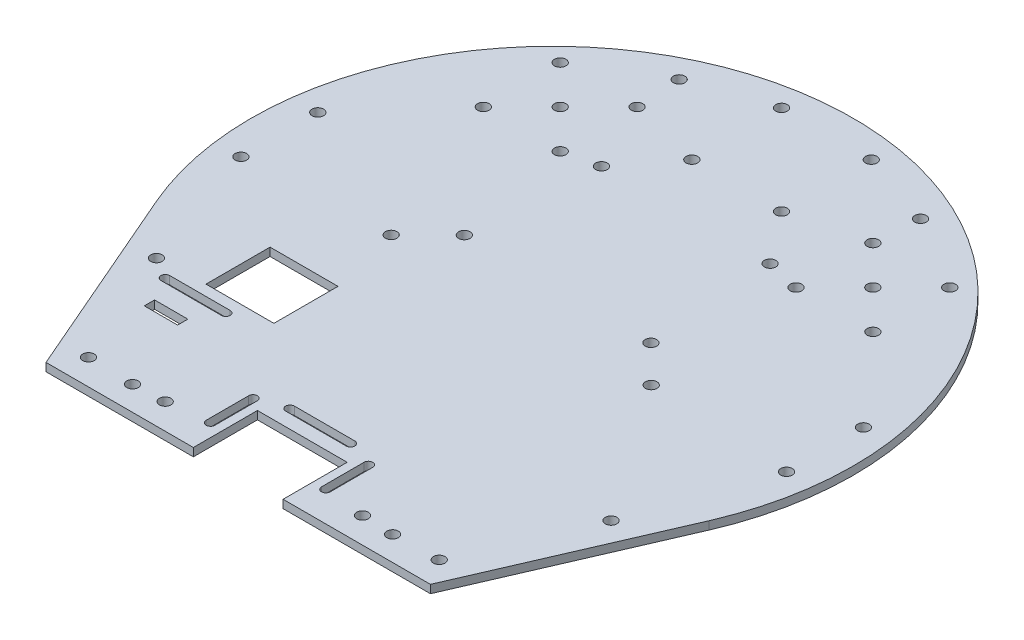
SolidWorks part; units mm, degrees
ref_plane "Front Plane" through (0, 0, 0) normal (0, 0, 1) x (1, 0, 0)
ref_plane "Top Plane" through (0, 0, 0) normal (0, 1, 0) x (1, 0, 0)
ref_plane "Right Plane" through (0, 0, 0) normal (1, 0, 0) x (0, 0, -1)
sketch "Sketch1" plane through (0, 0, 0) normal (0, 1, 0) x (1, 0, 0)
  circle A0 centre (0, 0) radius 117.5
  dimension "D1" = 235
extrude "Boss-Extrude1" add sketch "Sketch1" along normal blind 3.175
sketch "Sketch4" plane through (0, 0, 0) normal (0, 1, 0) x (1, 0, 0)
  line L2 (0, 0) -> (0, -53.2962) construction
  line L5 (107.8261, -46.6881) -> (75, -122.5)
  line L6 (75, -122.5) -> (-75, -122.5)
  line L7 (-75, -122.5) -> (-107.8261, -46.6881)
  line L8 (-107.8261, -46.6881) -> (107.8261, -46.6881)
  line L9 (0, -122.5) -> (0, -117.5) construction
  circle A3 centre (0, 0) radius 117.5 construction
  circle A4 centre (0, 0) radius 117.5 construction
  dimension "D1" = 150
  dimension "D2" = 5
extrude "Boss-Extrude2" add sketch "Sketch4" along normal up to surface (3.175 mm away) contours L5 | L8 L7 L6 L5 region at (0, 0, 82.3254) up to face at (0, 3.175, 117.5)
sketch "Sketch5" plane through (0, 0, 0) normal (0, 1, 0) x (1, 0, 0)
  line L0 (75, 117.5) -> (-0.1661, 117.5)
  line L1 (75, 117.5) -> (106.5777, 49.4717)
  line L2 (0, 0) -> (0, 46.0662) construction
  line L3 (-75, 117.5) -> (-0.1661, 117.5)
  line L4 (-75, 117.5) -> (-106.5777, 49.4717)
  circle A0 centre (0, 0) radius 117.5 construction
  arc A1 (106.5777, 49.4717) -> (-106.5777, 49.4717) centre (0, 0) ccw
  dimension "D1" = 150
extrude "Boss-Extrude3" [suppressed] add sketch "Sketch5" along normal up to surface (3.175 mm away) contours A1 L1 L0 | A1 L0 L3 L4 up to face at (0, 3.175, 43.547)
hole_wizard "#8 Clearance Hole1" positions "Sketch6" profile "Sketch7" hole size "#8" standard "ANSI Inch" end condition through all
sketch "Sketch6" plane through (0, 3.175, 0) normal (0, 1, 0) x (1, 0, 0)
  circle A0 centre (47.0917, 96.6365) radius 1.7272 construction
  circle A1 centre (17.5, 107) radius 1.7272 construction
  circle A2 centre (32.9, 52.1319) radius 1.7272 construction
  circle A3 centre (17.5, 72) radius 1.7272 construction
  circle A4 centre (-17.5, 72) radius 1.7272 construction
  circle A5 centre (-17.5, 107) radius 1.7272 construction
  circle A6 centre (-47.0917, 96.6365) radius 1.7272 construction
  circle A7 centre (-32.9, 52.1319) radius 1.7272 construction
  circle A8 centre (-106.4483, 15) radius 1.7272 construction
  circle A9 centre (-36.4, 2.1319) radius 1.7272 construction
  circle A10 centre (36.4, 2.1319) radius 1.7272 construction
  circle A11 centre (50.74, -12.09) radius 1.7 construction
  circle A12 centre (-50.74, -12.09) radius 1.7 construction
  circle A13 centre (-106.4483, -15) radius 1.7272 construction
  circle A14 centre (-88.6902, -65.7156) radius 1.7272 construction
  circle A15 centre (-68.4328, -112.5) radius 1.7272 construction
  circle A16 centre (-50.74, -113) radius 1.7 construction
  circle A17 centre (50.74, -113) radius 1.7 construction
  circle A18 centre (-38.5, -112.5) radius 1.7272 construction
  circle A19 centre (38.5, -112.5) radius 1.7272 construction
  circle A20 centre (68.4328, -112.5) radius 1.7272 construction
  circle A21 centre (88.6902, -65.7156) radius 1.7272 construction
  circle A22 centre (106.4483, -15) radius 1.7272 construction
  circle A23 centre (106.4483, 15) radius 1.7272 construction
  circle A24 centre (47.0917, 96.6365) radius 1.7272
  circle A25 centre (17.5, 107) radius 1.7272
  circle A26 centre (32.9, 52.1319) radius 1.7272
  circle A27 centre (17.5, 72) radius 1.7272
  circle A28 centre (-17.5, 72) radius 1.7272
  circle A29 centre (-17.5, 107) radius 1.7272
  circle A30 centre (-47.0917, 96.6365) radius 1.7272
  circle A31 centre (-32.9, 52.1319) radius 1.7272
  circle A32 centre (-106.4483, 15) radius 1.7272
  circle A33 centre (-36.4, 2.1319) radius 1.7272
  circle A34 centre (36.4, 2.1319) radius 1.7272
  circle A35 centre (50.74, -12.09) radius 1.7
  circle A36 centre (-50.74, -12.09) radius 1.7
  circle A37 centre (-106.4483, -15) radius 1.7272
  circle A38 centre (-88.6902, -65.7156) radius 1.7272
  circle A39 centre (-68.4328, -112.5) radius 1.7272
  circle A40 centre (-50.74, -113) radius 1.7
  circle A41 centre (50.74, -113) radius 1.7
  circle A42 centre (-38.5, -112.5) radius 1.7272
  circle A43 centre (38.5, -112.5) radius 1.7272
  circle A44 centre (68.4328, -112.5) radius 1.7272
  circle A45 centre (88.6902, -65.7156) radius 1.7272
  circle A46 centre (106.4483, -15) radius 1.7272
  circle A47 centre (106.4483, 15) radius 1.7272
  point P1 (47.0917, 96.6365)
  point P3 (17.5, 107)
  point P5 (32.9, 52.1319)
  point P7 (17.5, 72)
  point P9 (-17.5, 72)
  point P11 (-17.5, 107)
  point P13 (-47.0917, 96.6365)
  point P15 (-32.9, 52.1319)
  point P17 (-106.4483, 15)
  point P19 (-36.4, 2.1319)
  point P21 (36.4, 2.1319)
  point P23 (50.74, -12.09)
  point P25 (-50.74, -12.09)
  point P27 (-106.4483, -15)
  point P29 (-88.6902, -65.7156)
  point P31 (-68.4328, -112.5)
  point P33 (-50.74, -113)
  point P35 (50.74, -113)
  point P37 (-38.5, -112.5)
  point P39 (38.5, -112.5)
  point P41 (68.4328, -112.5)
  point P43 (88.6902, -65.7156)
  point P45 (106.4483, -15)
  point P47 (106.4483, 15)
sketch "Sketch7" plane through (47.0917, 3.175, -96.6365) normal (1, 0, 0) x (0, 0, 1)
  line L0 (0, 0) -> (0, 3.175)
  line L1 (0, 3.175) -> (2.2479, 3.175)
  line L2 (2.2479, 3.175) -> (2.2479, 0)
  line L5 (2.2479, 0) -> (0, 0)
  line L11 (0, -6.35) -> (0, 107.95) construction
  dimension "Thru Hole Dia." = 4.4958
  dimension "Thru Hole Depth" = 3.175
sketch "Sketch8" plane through (0, 3.175, 0) normal (0, 1, 0) x (1, 0, 0)
  line L0 (-61.9328, -80.21) -> (-74.9328, -80.21)
  line L1 (-74.9328, -80.21) -> (-74.9328, -84.21)
  line L2 (-74.9328, -84.21) -> (-61.9328, -84.21)
  line L3 (-61.9328, -84.21) -> (-61.9328, -80.21)
  line L4 (-62.4328, -80.71) -> (-74.4328, -80.71)
  line L5 (-62.4328, -83.71) -> (-62.4328, -80.71)
  line L6 (-74.4328, -83.71) -> (-62.4328, -83.71)
  line L7 (-74.4328, -80.71) -> (-74.4328, -83.71)
  line L8 (-62.4328, -80.71) -> (-74.4328, -80.71) construction
  line L9 (-62.4328, -83.71) -> (-62.4328, -80.71) construction
  line L10 (-74.4328, -83.71) -> (-62.4328, -83.71) construction
  line L11 (-74.4328, -80.71) -> (-74.4328, -83.71) construction
  dimension "D1" = 0
  dimension "D2" = 0.5
extrude "Cut-Extrude1" cut sketch "Sketch8" against normal through all
sketch "Sketch9" plane through (0, 3.175, 0) normal (0, 1, 0) x (1, 0, 0)
  line L0 (75, -122.5) -> (-75, -122.5) construction
  line L1 (-17.5, -122.5) -> (17.5, -122.5)
  line L2 (-17.5, -122.5) -> (-17.5, -97.5)
  line L3 (-17.5, -97.5) -> (17.5, -97.5)
  line L4 (17.5, -122.5) -> (17.5, -97.5)
  point P6 (0, -122.5)
  dimension "D1" = 25
  dimension "D2" = 35
extrude "Cut-Extrude2" cut sketch "Sketch9" against normal through all
hole_wizard "M3 Clearance Slot1" positions "Sketch10" profile "Sketch12" size "M3" standard "ANSI Metric" slot yes end condition through all
sketch "Sketch10" plane through (0, 3.175, 0) normal (0, 1, 0) x (1, 0, 0)
  line L6 (-78.9118, -70.71) -> (-68.4328, -70.71) construction
  line L8 (-68.4328, -77.71) -> (-68.4328, -70.71) construction
  line L9 (-62.4328, -77.71) -> (-74.4328, -77.71) construction
  line L11 (-81.9328, -70.71) -> (-54.9328, -70.71) construction
  line L12 (0, -97.5) -> (0, -90.5) construction
  line L13 (17.5, -97.5) -> (-17.5, -97.5) construction
  point P0 (-68.4328, -70.71)
  point P33 (0, -90.5)
  dimension "D1" = 27
  dimension "D2" = 7
  dimension "D3" = 7
sketch "Sketch12" plane through (-68.4328, 3.175, 70.71) normal (1, 0, 0) x (0, 0, 1)
  line L0 (0, 0) -> (0, 3.175)
  line L1 (0, 3.175) -> (1.7, 3.175)
  line L2 (1.7, 3.175) -> (1.7, 0)
  line L5 (1.7, 0) -> (0, 0)
  line L11 (0, -6.35) -> (0, 107.95) construction
  dimension "Thru Hole Dia." = 3.4
  dimension "Thru Hole Depth" = 3.175
hole_wizard "M3 Clearance Slot2" positions "Sketch13" profile "Sketch14" size "M3" standard "ANSI Metric" slot yes end condition through all
sketch "Sketch13" plane through (0, 3.175, 0) normal (0, 1, 0) x (1, 0, 0)
  line L0 (-22.5, -112.5) -> (-22.5, -92.5) construction
  line L1 (-22.5, -102.5) -> (22.5, -102.5) construction
  line L3 (0, -102.5) -> (0, 0) construction
  line L6 (-17.5, -122.5) -> (-75, -122.5) construction
  point P0 (-22.5, -102.5)
  point P4 (22.5, -102.5)
  dimension "D1" = 20
  dimension "D2" = 45
  dimension "D3" = 10
sketch "Sketch14" plane through (-22.5, 3.175, 102.5) normal (1, 0, 0) x (0, 0, 1)
  line L0 (0, 0) -> (0, 3.175)
  line L1 (0, 3.175) -> (1.7, 3.175)
  line L2 (1.7, 3.175) -> (1.7, 0)
  line L5 (1.7, 0) -> (0, 0)
  line L11 (0, -6.35) -> (0, 107.95) construction
  dimension "Thru Hole Dia." = 3.4
  dimension "Thru Hole Depth" = 3.175
sketch "Sketch15" plane through (0, 3.175, 0) normal (0, 1, 0) x (1, 0, 0)
  line L0 (-43.74, -44.835) -> (-43.74, -59.835) construction
  line L1 (-70.24, -39.835) -> (-43.74, -39.835)
  line L2 (-70.24, -39.835) -> (-70.24, -64.835)
  line L3 (-70.24, -64.835) -> (-43.74, -64.835)
  line L4 (-43.74, -39.835) -> (-43.74, -64.835)
  line L5 (-43.74, -44.835) -> (-43.74, -59.835) construction
  line L6 (-55.24, -12.09) -> (-55.24, -44.835) construction
  line L7 (-55.24, -12.09) -> (-55.24, -44.835) construction
  point P6 (-43.74, -52.335)
  dimension "D1" = 25
  dimension "D2" = 15
extrude "Cut-Extrude3" cut sketch "Sketch15" against normal through all
hole_wizard "#8 Clearance Hole2" positions "Sketch16" profile "Sketch17" hole size "#8" standard "ANSI Inch" end condition through all
sketch "Sketch16" plane through (0, 3.175, 0) normal (0, 1, 0) x (1, 0, 0)
  line L8 (-76, 49.1319) -> (-46, 49.1319)
  line L9 (-46, 49.1319) -> (-46, 79.1319)
  line L10 (-46, 79.1319) -> (-76, 79.1319)
  line L11 (-76, 79.1319) -> (-76, 49.1319)
  line L12 (-76, 49.1319) -> (-46, 49.1319)
  line L13 (-46, 49.1319) -> (-46, 79.1319)
  line L14 (-46, 79.1319) -> (-76, 79.1319)
  line L15 (-76, 79.1319) -> (-76, 49.1319)
  line L24 (46, 49.1319) -> (76, 49.1319)
  line L25 (76, 49.1319) -> (76, 79.1319)
  line L26 (76, 79.1319) -> (46, 79.1319)
  line L27 (46, 79.1319) -> (46, 49.1319)
  line L28 (46, 49.1319) -> (76, 49.1319)
  line L29 (76, 49.1319) -> (76, 79.1319)
  line L30 (76, 79.1319) -> (46, 79.1319)
  line L31 (46, 79.1319) -> (46, 49.1319)
  line L32 (-76, 79.1319) -> (-46, 49.1319)
  line L34 (46, 79.1319) -> (76, 49.1319)
  point P9 (-76, 49.1319)
  point P10 (-46, 49.1319)
  point P12 (-46, 79.1319)
  point P13 (-76, 79.1319)
  point P25 (46, 49.1319)
  point P26 (76, 49.1319)
  point P28 (76, 79.1319)
  point P29 (46, 79.1319)
  point P65 (-61, 64.1319)
  point P67 (61, 64.1319)
  dimension "D1" = 0
  dimension "D2" = 0
sketch "Sketch17" plane through (-76, 3.175, -49.1319) normal (1, 0, 0) x (0, 0, 1)
  line L0 (0, 0) -> (0, 3.175)
  line L1 (0, 3.175) -> (2.2479, 3.175)
  line L2 (2.2479, 3.175) -> (2.2479, 0)
  line L5 (2.2479, 0) -> (0, 0)
  line L11 (0, -6.35) -> (0, 107.95) construction
  dimension "Thru Hole Dia." = 4.4958
  dimension "Thru Hole Depth" = 3.175
